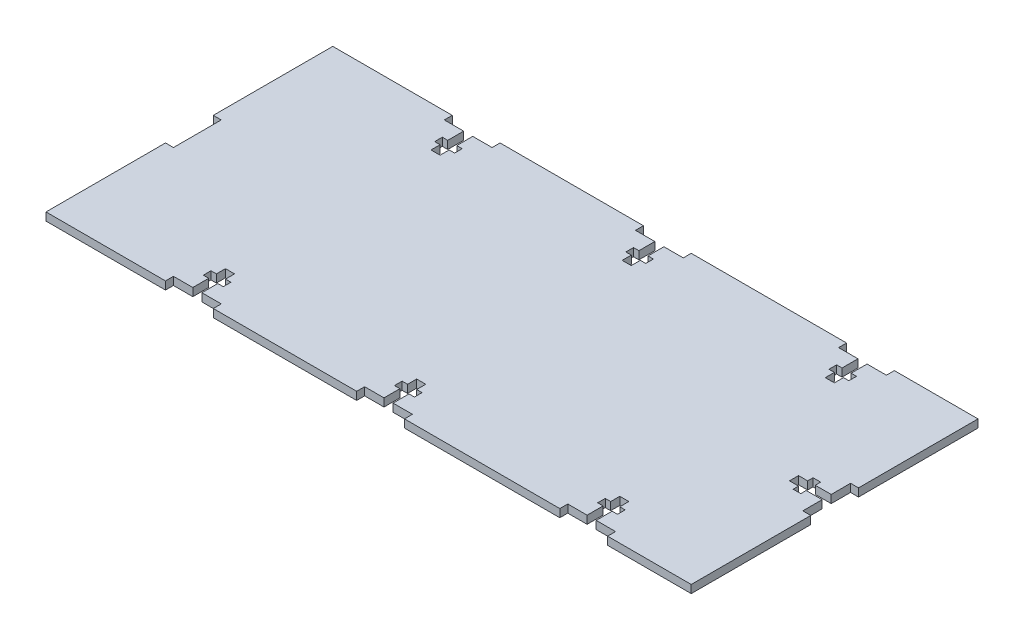
SolidWorks part; units mm, degrees
ref_plane "Front Plane" through (0, 0, 0) normal (0, 0, 1) x (1, 0, 0)
ref_plane "Top Plane" through (0, 0, 0) normal (0, 1, 0) x (1, 0, 0)
ref_plane "Right Plane" through (0, 0, 0) normal (1, 0, 0) x (0, 0, -1)
sketch "Sketch2" plane through (0, 0, 0) normal (0, 1, 0) x (1, 0, 0)
  line L0 (-102.87, -45.72) -> (-64.77, -45.72)
  line L1 (-102.87, 45.72) -> (102.87, 45.72) construction
  line L2 (-102.87, 45.72) -> (-102.87, -45.72) construction
  line L3 (-102.87, -45.72) -> (102.87, -45.72) construction
  line L4 (102.87, 45.72) -> (102.87, -45.72) construction
  line L5 (-102.87, 45.72) -> (102.87, -45.72) construction
  line L6 (-102.87, -45.72) -> (102.87, 45.72) construction
  line L7 (-64.77, -45.72) -> (-64.77, -43.18)
  line L9 (-49.53, -43.18) -> (-49.53, -45.72)
  line L10 (-49.53, -45.72) -> (-3.81, -45.72)
  line L11 (-3.81, -45.72) -> (-3.81, -43.18)
  line L12 (-3.81, -43.18) -> (11.43, -43.18) construction
  line L13 (11.43, -43.18) -> (11.43, -45.72)
  line L14 (11.43, -45.72) -> (60.96, -45.72)
  line L15 (60.96, -45.72) -> (60.96, -43.18)
  line L16 (60.96, -43.18) -> (76.2, -43.18) construction
  line L17 (76.2, -43.18) -> (76.2, -45.72)
  line L18 (76.2, -45.72) -> (102.87, -45.72)
  line L21 (-102.87, 0) -> (102.87, 0) construction
  line L22 (76.2, 43.18) -> (76.2, 45.72)
  line L23 (60.96, 43.18) -> (76.2, 43.18) construction
  line L24 (60.96, 45.72) -> (60.96, 43.18)
  line L25 (11.43, 43.18) -> (11.43, 45.72)
  line L26 (-3.81, 43.18) -> (11.43, 43.18) construction
  line L27 (-3.81, 45.72) -> (-3.81, 43.18)
  line L28 (-49.53, 43.18) -> (-49.53, 45.72)
  line L29 (-64.77, 43.18) -> (-49.53, 43.18) construction
  line L30 (-64.77, 45.72) -> (-64.77, 43.18)
  line L31 (-102.87, 45.72) -> (-64.77, 45.72)
  line L32 (-49.53, 45.72) -> (-3.81, 45.72)
  line L33 (11.43, 45.72) -> (60.96, 45.72)
  line L34 (76.2, 45.72) -> (102.87, 45.72)
  line L35 (-102.87, 45.72) -> (-102.87, 7.62)
  line L36 (-102.87, 7.62) -> (-100.33, 7.62)
  line L37 (-100.33, 7.62) -> (-100.33, -7.62)
  line L38 (-100.33, -7.62) -> (-102.87, -7.62)
  line L39 (-102.87, -7.62) -> (-102.87, -45.72)
  line L40 (0, 45.72) -> (0, -45.72) construction
  line L41 (100.33, -7.62) -> (102.87, -7.62)
  line L42 (102.87, 7.62) -> (100.33, 7.62)
  line L43 (100.33, 7.62) -> (100.33, -7.62) construction
  line L44 (102.87, 45.72) -> (102.87, 7.62)
  line L45 (102.87, -7.62) -> (102.87, -45.72)
  line L46 (-58.5978, -43.18) -> (-58.5978, -38.1)
  line L47 (-58.5978, -38.1) -> (-60.325, -38.1)
  line L48 (-60.325, -38.1) -> (-60.325, -35.668)
  line L49 (-60.325, -35.668) -> (-58.5978, -35.668)
  line L50 (-58.5978, -35.668) -> (-58.5978, -32.766)
  line L51 (-58.5978, -32.766) -> (-55.7022, -32.766)
  line L52 (-64.77, -43.18) -> (-58.5978, -43.18)
  line L53 (-49.53, -43.18) -> (-55.7022, -43.18)
  line L54 (-55.7022, -43.18) -> (-55.7022, -38.1)
  line L55 (-55.7022, -38.1) -> (-53.975, -38.1)
  line L56 (-53.975, -38.1) -> (-53.975, -35.668)
  line L57 (-64.77, -43.18) -> (-49.53, -43.18) construction
  line L58 (-57.15, -43.18) -> (-57.15, -32.766) construction
  line L59 (-53.975, -35.668) -> (-55.7022, -35.668)
  line L60 (-55.7022, -35.668) -> (-55.7022, -32.766)
  line L61 (-3.81, -43.18) -> (2.3622, -43.18)
  line L62 (2.3622, -43.18) -> (2.3622, -38.1)
  line L63 (2.3622, -38.1) -> (0.635, -38.1)
  line L64 (0.635, -38.1) -> (0.635, -35.6679)
  line L65 (0.635, -35.6679) -> (2.3622, -35.6679)
  line L66 (2.3622, -35.6679) -> (2.3622, -32.766)
  line L67 (2.3622, -32.766) -> (5.2578, -32.766)
  line L68 (3.81, -43.18) -> (3.81, -32.766) construction
  line L69 (11.43, -43.18) -> (5.2578, -43.18)
  line L70 (5.2578, -43.18) -> (5.2578, -38.1)
  line L71 (5.2578, -38.1) -> (6.985, -38.1)
  line L72 (6.985, -38.1) -> (6.985, -35.6679)
  line L73 (6.985, -35.6679) -> (5.2578, -35.6679)
  line L74 (5.2578, -35.6679) -> (5.2578, -32.766)
  line L75 (68.58, -43.18) -> (68.58, -32.766) construction
  line L76 (60.96, -43.18) -> (67.1322, -43.18)
  line L77 (67.1322, -43.18) -> (67.1322, -38.1)
  line L78 (67.1322, -38.1) -> (65.405, -38.1)
  line L79 (65.405, -38.1) -> (65.405, -35.6679)
  line L80 (65.405, -35.6679) -> (67.1322, -35.6679)
  line L81 (67.1322, -35.6679) -> (67.1322, -32.766)
  line L82 (67.1322, -32.766) -> (70.0278, -32.766)
  line L83 (70.0278, -35.6679) -> (70.0278, -32.766)
  line L84 (71.755, -35.6679) -> (70.0278, -35.6679)
  line L85 (71.755, -38.1) -> (71.755, -35.6679)
  line L86 (70.0278, -38.1) -> (71.755, -38.1)
  line L87 (76.2, -43.18) -> (70.0278, -43.18)
  line L88 (70.0278, -43.18) -> (70.0278, -38.1)
  line L89 (76.2, 43.18) -> (70.0278, 43.18)
  line L90 (70.0278, 43.18) -> (70.0278, 38.1)
  line L91 (70.0278, 38.1) -> (71.755, 38.1)
  line L92 (71.755, 38.1) -> (71.755, 35.6679)
  line L93 (71.755, 35.6679) -> (70.0278, 35.6679)
  line L94 (70.0278, 35.6679) -> (70.0278, 32.766)
  line L95 (67.1322, 32.766) -> (70.0278, 32.766)
  line L96 (67.1322, 35.6679) -> (67.1322, 32.766)
  line L97 (65.405, 35.6679) -> (67.1322, 35.6679)
  line L98 (65.405, 38.1) -> (65.405, 35.6679)
  line L99 (67.1322, 38.1) -> (65.405, 38.1)
  line L100 (67.1322, 43.18) -> (67.1322, 38.1)
  line L101 (60.96, 43.18) -> (67.1322, 43.18)
  line L102 (11.43, 43.18) -> (5.2578, 43.18)
  line L103 (5.2578, 43.18) -> (5.2578, 38.1)
  line L104 (5.2578, 38.1) -> (6.985, 38.1)
  line L105 (6.985, 38.1) -> (6.985, 35.6679)
  line L106 (6.985, 35.6679) -> (5.2578, 35.6679)
  line L107 (5.2578, 35.6679) -> (5.2578, 32.766)
  line L108 (2.3622, 32.766) -> (5.2578, 32.766)
  line L109 (0.635, 35.6679) -> (2.3622, 35.6679)
  line L110 (2.3622, 38.1) -> (0.635, 38.1)
  line L111 (0.635, 38.1) -> (0.635, 35.6679)
  line L112 (2.3622, 43.18) -> (2.3622, 38.1)
  line L113 (-3.81, 43.18) -> (2.3622, 43.18)
  line L114 (-49.53, 43.18) -> (-55.7022, 43.18)
  line L115 (-55.7022, 43.18) -> (-55.7022, 38.1)
  line L116 (-55.7022, 38.1) -> (-53.975, 38.1)
  line L117 (-53.975, 38.1) -> (-53.975, 35.6679)
  line L118 (-53.975, 35.6679) -> (-55.7022, 35.6679)
  line L119 (-55.7022, 35.6679) -> (-55.7022, 32.766)
  line L120 (-58.5978, 32.766) -> (-55.7022, 32.766)
  line L121 (-58.5978, 35.6679) -> (-58.5978, 32.766)
  line L122 (-60.325, 35.6679) -> (-58.5978, 35.6679)
  line L123 (-60.325, 38.1) -> (-60.325, 35.6679)
  line L124 (-58.5978, 38.1) -> (-60.325, 38.1)
  line L125 (-58.5978, 43.18) -> (-58.5978, 38.1)
  line L126 (-64.77, 43.18) -> (-58.5978, 43.18)
  line L127 (2.3622, 35.6679) -> (2.3622, 32.766)
  line L128 (100.33, -1.4478) -> (95.25, -1.4478)
  line L129 (95.25, -1.4478) -> (95.25, -3.175)
  line L130 (95.25, -3.175) -> (92.8179, -3.175)
  line L131 (92.8179, -3.175) -> (92.8179, -1.4478)
  line L132 (92.8179, -1.4478) -> (89.916, -1.4478)
  line L133 (89.916, -1.4478) -> (89.916, 1.4478)
  line L134 (100.33, -1.4478) -> (100.33, -7.62)
  line L135 (92.8179, 1.4478) -> (89.916, 1.4478)
  line L136 (92.8179, 3.175) -> (92.8179, 1.4478)
  line L137 (95.25, 3.175) -> (92.8179, 3.175)
  line L138 (95.25, 1.4478) -> (95.25, 3.175)
  line L139 (100.33, 1.4478) -> (95.25, 1.4478)
  line L140 (100.33, 1.4478) -> (100.33, 7.62)
  point P0 (0, 0)
  point P128 (89.916, 0)
  dimension "D1" = 205.74
  dimension "D2" = 91.44
  dimension "D3" = 38.1
  dimension "D4" = 15.24
  dimension "D5" = 2.54
  dimension "D6" = 45.72
  dimension "D7" = 49.53
  dimension "D8" = 15.24
  dimension "D9" = 2.54
  dimension "D10" = 12.954
  dimension "D11" = 5.08
  dimension "D12" = 2.432
  dimension "D13" = 6.35
  dimension "D14" = 2.8956
  dimension "D15" = 12.954
  dimension "D16" = 5.08
  dimension "D17" = 2.432
  dimension "D18" = 6.35
  dimension "D19" = 2.8956
  dimension "D20" = 12.954
  dimension "D21" = 5.08
  dimension "D22" = 2.432
  dimension "D23" = 6.35
  dimension "D24" = 2.8956
  dimension "D25" = 12.954
  dimension "D26" = 2.432
  dimension "D27" = 5.08
  dimension "D28" = 2.8956
  dimension "D29" = 6.35
extrude "Boss-Extrude1" add sketch "Sketch2" against normal blind 2.54
